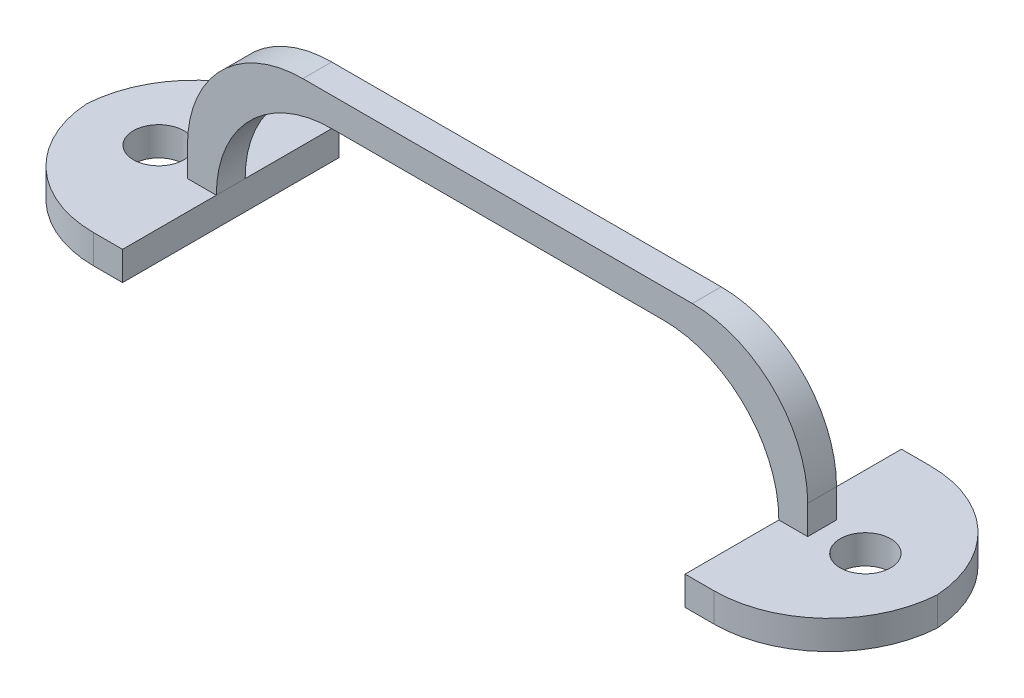
SolidWorks part; units mm, degrees
ref_plane "前视基准面" through (0, 0, 0) normal (0, 0, 1) x (1, 0, 0)
ref_plane "上视基准面" through (0, 0, 0) normal (0, 1, 0) x (1, 0, 0)
ref_plane "右视基准面" through (0, 0, 0) normal (1, 0, 0) x (0, 0, -1)
other "Configuration Table"
sketch "Sketch3" plane through (0, 0, 0) normal (0, 1, 0) x (1, 0, 0)
  line L1 (-22.6095, -1.173) -> (-12.6095, -1.173)
  line L2 (-22.6095, -1.173) -> (-22.6095, -16.173)
  line L3 (-22.6095, -16.173) -> (-12.6095, -16.173)
  line L4 (-12.6095, -1.173) -> (-12.6095, -16.173)
  line L5 (26.3905, -1.173) -> (36.3905, -1.173)
  line L6 (26.3905, -1.173) -> (26.3905, -16.173)
  line L7 (26.3905, -16.173) -> (36.3905, -16.173)
  line L8 (36.3905, -1.173) -> (36.3905, -16.173)
  circle A0 centre (-17.6095, -8.673) radius 1.75
  circle A1 centre (31.3905, -8.673) radius 1.75
  point P10 (0, 0)
  point P11 (-17.6095, -1.173)
  point P12 (31.3905, -1.173)
  point P13 (36.3905, -8.673)
  point P14 (-12.6095, -8.673)
  dimension "D3" = 3.5
  dimension "D4" = 3.5
  dimension "D1" = 10
  dimension "D2" = 15
  dimension "D5" = 49
extrude "Boss-Extrude1" add sketch "Sketch3" along normal blind 2 contours L2 L1 L4 L3 | L6 L5 L8 L7 | A0 | A1
ref_plane "Plane1" through (0, 0, 8.673) normal (0, 0, 1) x (1, 0, 0)
sketch "Sketch4" plane through (0, 0, 8.673) normal (0, 0, 1) x (1, 0, 0)
  line L0 (-12.6095, 2) -> (-12.6095, 10)
  line L1 (-22.6095, 2) -> (-12.6095, 2) construction
  line L2 (-12.6095, 2) -> (-12.6095, 0) construction
  line L3 (-12.6095, 10) -> (26.3905, 10)
  line L4 (26.3905, 10) -> (26.3905, 2)
  line L5 (26.3905, 2) -> (28.3905, 2)
  line L6 (26.3905, 2) -> (36.3905, 2) construction
  line L7 (28.3905, 2) -> (28.3905, 12)
  line L8 (28.3905, 12) -> (-14.6095, 12)
  line L9 (-14.6095, 12) -> (-14.6095, 2)
  line L10 (-12.6095, 2) -> (-14.6095, 2)
  dimension "D1" = 2
  dimension "D2" = 2
  dimension "D3" = 10
  dimension "D4" = 2
extrude "Boss-Extrude2" add sketch "Sketch4" along normal blind 1 and the other way blind 1
fillet "Fillet1" radius 8 8 edges at (-22.6095, 1, 1.173) (-22.6095, 1, 16.173) (36.3905, 1, 1.173) (36.3905, 1, 16.173) (28.3905, 12, 8.673) (26.3905, 10, 8.673) (-14.6095, 12, 8.673) (-12.6095, 10, 8.673)
